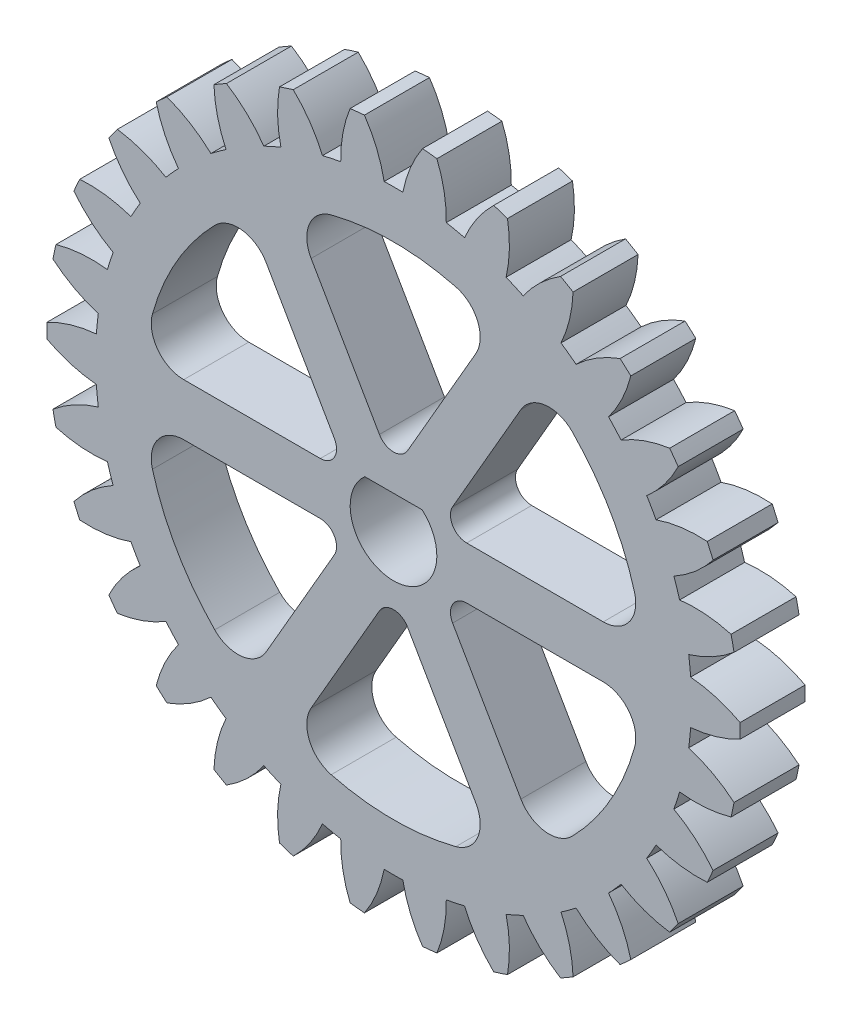
SolidWorks part; units mm, degrees
ref_plane "Front Plane" through (0, 0, 0) normal (0, 0, 1) x (1, 0, 0)
ref_plane "Top Plane" through (0, 0, 0) normal (0, 1, 0) x (1, 0, 0)
ref_plane "Right Plane" through (0, 0, 0) normal (1, 0, 0) x (0, 0, -1)
sketch "Sketch1" plane through (0, 0, 0) normal (0, 0, 1) x (1, 0, 0)
  circle A0 centre (0, 0) radius 16
  dimension "addendumDiameter " = 32
extrude "Boss-Extrude1" add sketch "Sketch1" along normal blind 3
sketch "Sketch2" plane through (0, 0, 3) normal (0, 0, 1) x (1, 0, 0)
  line L0 (0, 0) -> (0, 31.2008) construction
  line L1 (0, 0) -> (-2.6449, 25.1645) construction
  line L2 (-0.7752, 14.8891) -> (-1.5563, 14.807) construction
  circle A0 centre (0, 0) radius 13.75 construction
  circle A1 centre (0, 0) radius 14.0954 construction
  circle A2 centre (0, 0) radius 15 construction
  arc A3 (-1.3398, 15.9438) -> (-0.431, 13.7432) centre (-6.3208, 12.5987) cw
  arc A4 (-1.3398, 15.9438) -> (1.3398, 15.9438) centre (0, 0) cw
  arc A5 (-0.431, 13.7432) -> (0.431, 13.7432) centre (0, 0) cw
  circle A6 centre (0, 0) radius 16 construction
  arc A7 (1.3398, 15.9438) -> (0.431, 13.7432) centre (6.3208, 12.5987) ccw
  dimension "dedendumCircle" = 27.5
  dimension "baseDiameter" = 28.1908
  dimension "pitchDiameter" = 30
  dimension "D2" = 6
  dimension "D1" = 6
  dimension "D3" = 0.7854
extrude "Cut-Extrude1" cut sketch "Sketch2" against normal through all
pattern_circular "CirPattern1" count 30 over 360 about axis through (0, 0, 3) along (0, 0, 1) of "Cut-Extrude1"
sketch "Sketch3" plane through (0, 0, 3) normal (0, 0, 1) x (1, 0, 0)
  line L0 (0, 0) -> (-35.4164, 0) construction
  line L1 (0, 0) -> (-16.4465, 28.4861) construction
  line L5 (-3.3775, 1.2) -> (-9.6805, 1.2)
  line L6 (-2.728, 2.325) -> (-5.8795, 7.7836)
  arc A1 (-11.1254, 3.103) -> (-8.25, 8.0834) centre (0, 0) cw
  arc A2 (-5.8795, 7.7836) -> (-8.25, 8.0834) centre (-7.1785, 7.0336) ccw
  circle A3 centre (0, 0) radius 11.55 construction
  arc A4 (-9.6805, 1.2) -> (-11.1254, 3.103) centre (-9.6805, 2.7) cw
  arc A5 (-3.3775, 1.2) -> (-2.728, 2.325) centre (-3.3775, 1.95) ccw
  point P10 (-6.783, 9.3485)
  point P14 (-11.4875, 1.2)
  dimension "D5" = 23.1
  dimension "D3" = 1.5
  dimension "D4" = 0.75
  dimension "D1" = 60
  dimension "D2" = 1.2
extrude "Cut-Extrude3" cut sketch "Sketch3" against normal through all
pattern_circular "CirPattern2" count 6 over 360 about axis through (0, 0, 3) along (0, 0, -1) of "Cut-Extrude3"
sketch "Sketch4" plane through (0, 0, 3) normal (0, 0, 1) x (1, 0, 0)
  line L0 (-1.3229, 1.5) -> (1.3229, 1.5)
  line L1 (1.65, 0) -> (-1.65, 0) construction
  arc A0 (-1.3229, 1.5) -> (1.3229, 1.5) centre (0, 0) ccw
  dimension "D1" = 2
  dimension "D2" = 1.5
extrude "Cut-Extrude4" cut sketch "Sketch4" against normal through all
equation "\"module\" = 1.0"
equation "\"teeth\"= 30"
equation "\"pressureAngle\"= 20deg"
equation "\"gearThickness\"= 3"
equation "\"addendumFactor\"= 1"
equation "\"dedendumFactor\"= 1.25"
equation "\"pitch\"= 1/\"module\""
equation "\"pitchDiameter\"= \"teeth\" / \"pitch\""
equation "\"addendum\"= \"addendumFactor\" / \"pitch\""
equation "\"dedendum\"= \"dedendumFactor\" / \"pitch\""
equation "\"addendumDiameter @Sketch1\"= \"pitchDiameter\" + 2 * \"addendum\""
equation "\"D1@Boss-Extrude1\"= \"gearThickness\""
equation "\"dedendumCircle@Sketch2\" = \"pitchDiameter\" - 2 * \"dedendum\""
equation "\"baseDiameter@Sketch2\"=\"pitchDiameter\" * cos ( \"pressureAngle\" )"
equation "\"pitchDiameter@Sketch2\"=\"pitchDiameter\""
equation "\"D1@Sketch2\"=180/\"teeth\""
equation "\"D2@Sketch2\"=\"pitchDiameter\"/5"
equation "\"D3@Sketch2\"=PI / 2 / \"pitch\" / 2"
equation "\"D1@CirPattern1\"=\"teeth\""
equation "\"D5@Sketch3\"=\"pitchDiameter\"*.77"
equation "\"D2@Sketch3\"=\"module\"*\"teeth\"*.04"
